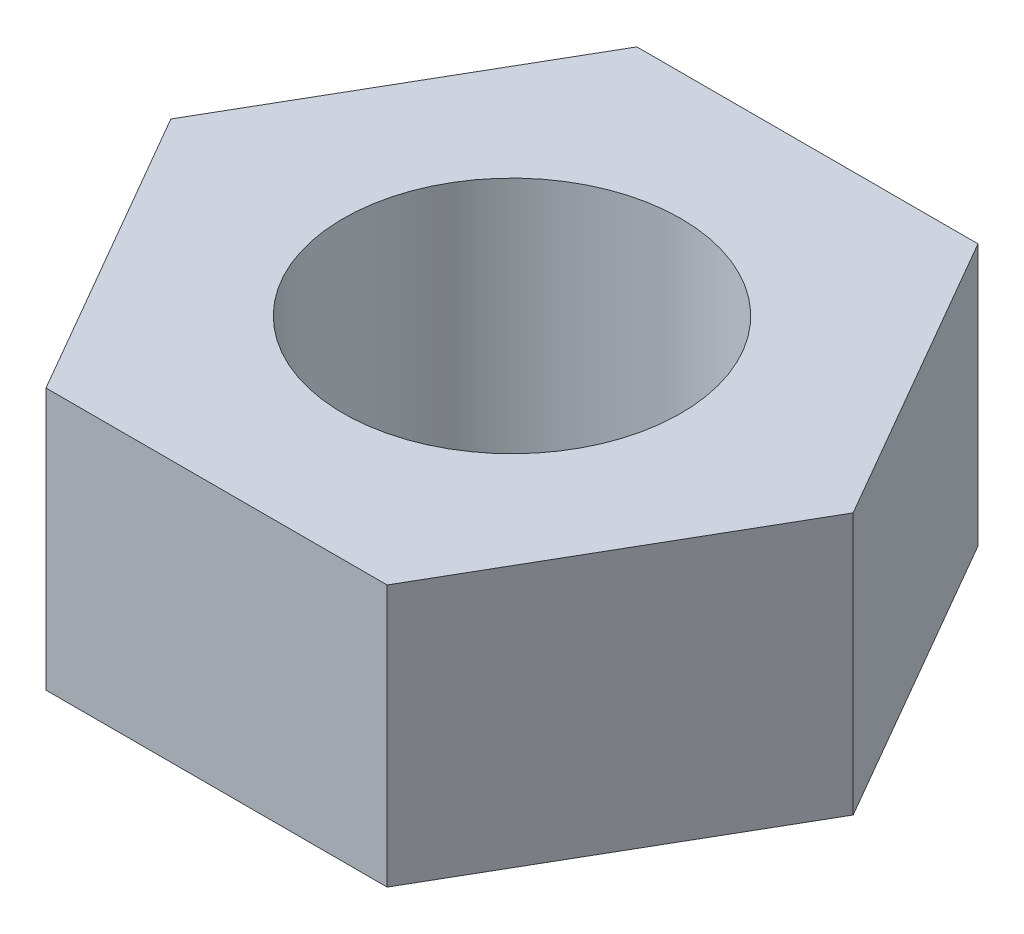
SolidWorks part; units mm, degrees
ref_plane "前视基准面" through (0, 0, 0) normal (0, 0, 1) x (1, 0, 0)
ref_plane "上视基准面" through (0, 0, 0) normal (0, 1, 0) x (1, 0, 0)
ref_plane "右视基准面" through (0, 0, 0) normal (1, 0, 0) x (0, 0, -1)
other "Configuration Table"
sketch "草图1" plane through (0, 0, 0) normal (0, 1, 0) x (1, 0, 0)
  line L1 (4.0415, 0) -> (2.0207, 3.5)
  line L2 (2.0207, 3.5) -> (-2.0207, 3.5)
  line L3 (-2.0207, 3.5) -> (-4.0415, 0)
  line L4 (-4.0415, 0) -> (-2.0207, -3.5)
  line L5 (-2.0207, -3.5) -> (2.0207, -3.5)
  line L6 (2.0207, -3.5) -> (4.0415, 0)
  circle A0 centre (0, 0) radius 3.5 construction
  dimension "D1" = 7
extrude "凸台-拉伸1" add sketch "草图1" along normal blind 3.1
sketch "草图3" plane through (0, 0, 0) normal (0, -1, 0) x (1, 0, 0)
  circle A0 centre (0, 0) radius 2
  dimension "D1" = 4
extrude "切除-拉伸1" cut sketch "草图3" against normal through all
ref_axis "基准轴1" through (0, 6.3881, 0) along (0, -1, 0)
